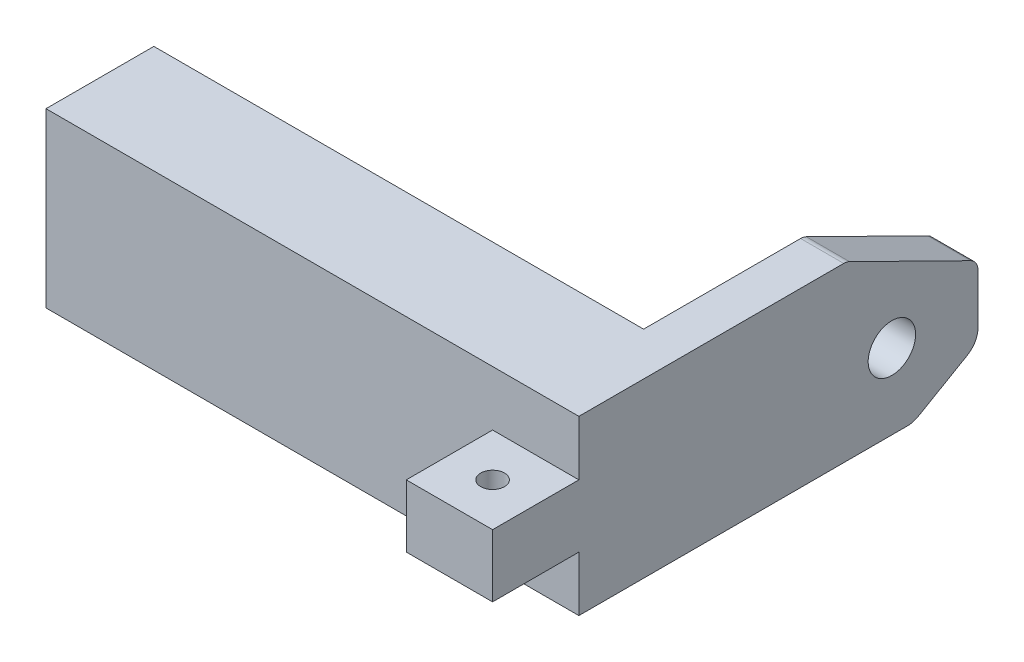
SolidWorks part; units mm, degrees
material "PLA"
ref_plane "Front Plane" through (0, 0, 0) normal (0, 0, 1) x (1, 0, 0)
ref_plane "Top Plane" through (0, 0, 0) normal (0, 1, 0) x (1, 0, 0)
ref_plane "Right Plane" through (0, 0, 0) normal (1, 0, 0) x (0, 0, -1)
sketch "Sketch1" plane through (0, 0, 0) normal (1, 0, 0) x (0, 0, -1)
  line L1 (-35.9146, 20.1296) -> (56.5854, 20.1296)
  line L2 (-35.9146, 20.1296) -> (-35.9146, -19.8704)
  line L3 (-35.9146, -19.8704) -> (56.5854, -19.8704)
  line L4 (56.5854, 20.1296) -> (56.5854, -19.8704)
  dimension "D1" = 92.5
  dimension "D2" = 40
extrude "Boss-Extrude1" add sketch "Sketch1" along normal blind 10
sketch "Sketch4" plane through (0, 0, 0) normal (-1, 0, 0) x (0, 0, 1)
  line L11 (-56.5854, 20.1296) -> (35.9146, 20.1296) construction
  line L12 (10.9146, 20.1296) -> (35.9146, 20.1296)
  line L13 (10.9146, 20.1296) -> (10.9146, -19.8704)
  line L14 (10.9146, -19.8704) -> (35.9146, -19.8704)
  line L15 (35.9146, 20.1296) -> (35.9146, -19.8704)
  line L16 (10.9146, 20.1296) -> (35.9146, -19.8704) construction
  line L17 (10.9146, -19.8704) -> (35.9146, 20.1296) construction
  line L18 (18.2896, 12.7546) -> (18.2896, -12.4954)
  line L19 (18.2896, -12.4954) -> (28.5396, -12.4954)
  line L20 (28.5396, 12.7546) -> (28.5396, -12.4954)
  line L21 (18.2896, 12.7546) -> (28.5396, 12.7546)
  point P4 (23.4146, 0.1296)
  dimension "D1" = 25
  dimension "D2" = 7.375
sketch "Sketch5" plane through (0, 0, 0) normal (-1, 0, 0) x (0, 0, 1)
  line L0 (35.9146, -19.8704) -> (-56.5854, -19.8704) construction
  line L2 (35.9146, 20.1296) -> (35.9146, -19.8704) construction
  circle A0 centre (-36.6254, -2.4304) radius 5.5
  dimension "D1" = 11
  dimension "D2" = 17.44
  dimension "D3" = 72.54
extrude "Cut-Extrude1" cut sketch "Sketch5" against normal blind 27
extrude "Boss-Extrude7" add sketch "Sketch4" along normal blind 113.5
fillet "Fillet1" radius 3 4 edges at (-113.5, -12.4954, 23.4146) (-113.5, 0.1296, 28.5396) (-113.5, 12.7546, 23.4146) (-113.5, 0.1296, 18.2896)
chamfer "Chamfer1" distance 15 angle 63.75 1 edges at (5, 20.1296, -56.5854) first distance on face at (5, 0.1296, -56.5854)
fillet "Fillet3" radius 3 2 edges at (5, 20.1296, -26.1684) (5, 5.1296, -56.5854)
chamfer "Chamfer3" distance 15 angle 30 1 edges at (5, -19.8704, -56.5854) first distance on face at (-34.5, -19.8704, -3.252)
fillet "Fillet7" radius 5 2 edges at (5, -19.8704, -41.5854) (5, -11.2102, -56.5854)
ref_plane "Plane1" through (10, 20.1296, 35.9146) normal (0, 0, 1) x (1, 0, 0)
sketch "Sketch7" plane through (10, 20.1296, 35.9146) normal (0, 0, 1) x (1, 0, 0)
  line L0 (-20, 0) -> (0, 0) construction
  line L1 (0, 0) -> (-123.5, 0) construction
  line L2 (0, 0) -> (0, -40) construction
  line L3 (-10, 0) -> (-10, -40) construction
  line L4 (0, -40) -> (-123.5, -40) construction
  line L6 (-20, -12.75) -> (0, -12.75)
  line L7 (-20, -12.75) -> (-20, -27.25)
  line L8 (-20, -27.25) -> (0, -27.25)
  line L9 (0, -12.75) -> (0, -27.25)
  line L10 (-20, -12.75) -> (0, -27.25) construction
  line L11 (-20, -27.25) -> (0, -12.75) construction
  point P10 (-10, -20)
  dimension "D1" = 20
  dimension "D2" = 14.5
extrude "Boss-Extrude8" add sketch "Sketch7" along normal blind 20
hole_wizard "M5 Clearance Hole1" positions "Sketch8" profile "Sketch9" hole size "M5" standard "ANSI Metric" end condition through all
sketch "Sketch8" plane through (0, 7.3796, 0) normal (0, 1, 0) x (1, 0, 0)
  line L0 (10, -55.9146) -> (-10, -55.9146) construction
  point P0 (0, -45.9146)
  dimension "D1" = 10
sketch "Sketch9" plane through (0, 7.3796, 45.9146) normal (1, 0, 0) x (0, 0, 1)
  line L0 (0, 0) -> (0, 27.25)
  line L1 (0, 27.25) -> (2.75, 27.25)
  line L2 (2.75, 27.25) -> (2.75, 0)
  line L5 (2.75, 0) -> (0, 0)
  line L11 (0, -6.35) -> (0, 107.95) construction
  dimension "Thru Hole Dia." = 5.5
  dimension "Thru Hole Depth" = 27.25
